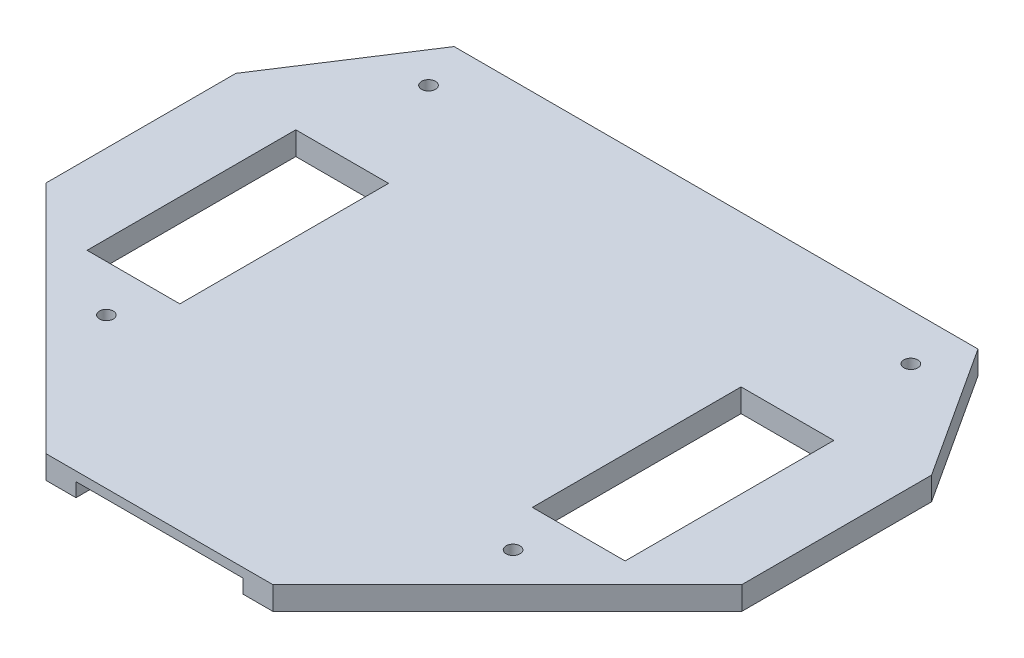
SolidWorks part; units mm, degrees
material "PMMA"
ref_plane "Front Plane" through (0, 0, 0) normal (0, 0, 1) x (1, 0, 0)
ref_plane "Top Plane" through (0, 0, 0) normal (0, 1, 0) x (1, 0, 0)
ref_plane "Right Plane" through (0, 0, 0) normal (1, 0, 0) x (0, 0, -1)
sketch "Sketch3" plane through (0, -40, 0) normal (0, -1, 0) x (-1, 0, 0)
  line L1 (27.5392, -110) -> (76.462, -110)
  line L2 (-23, -59.4608) -> (-23, -18.5314)
  line L3 (-4.4715, 10) -> (108.4727, 10)
  line L4 (127, -59.462) -> (127, -18.5295)
  line L5 (108.4727, 10) -> (127, -18.5295)
  line L6 (108.1379, 10.5156) -> (115.3271, -0.5548) construction
  line L7 (-4.4715, 10) -> (-23, -18.5314)
  line L8 (-17.9432, -10.7447) -> (2.4807, 20.7055) construction
  line L9 (127, -59.462) -> (76.462, -110)
  line L10 (52.0006, 10) -> (52.0006, -110) construction
  line L11 (27.5392, -110) -> (-23, -59.4608)
  dimension "D1" = 150
  dimension "D2" = 10
  dimension "D3" = 23
  dimension "D4" = 120
  dimension "D5" = 135
  dimension "D6" = 135
  dimension "D7" = 33
  dimension "D8" = 33
extrude "Boss-Extrude1" add sketch "Sketch3" along normal blind 5
hole_wizard "Ø3.0 (3) Diameter Hole1" positions "Sketch5" profile "Sketch4" hole size "Ø3.0" standard "ANSI Metric"
sketch "Sketch5" plane through (0, -45, 0) normal (0, -1, 0) x (-1, 0, 0)
  circle A0 centre (8.157, -77.6082) radius 1.5 construction
  circle A1 centre (95.8382, -77.6082) radius 1.5 construction
  circle A2 centre (103.9952, 0) radius 1.5 construction
  circle A3 centre (0, 0) radius 1.5 construction
  point P0 (8.157, -77.6082)
  point P3 (95.8382, -77.6082)
  point P6 (103.9952, 0)
  point P9 (0, 0)
sketch "Sketch4" plane through (-8.157, -45, 77.6082) normal (1, 0, 0) x (0, 0, -1)
  line L0 (0, 0) -> (0, 6.9013)
  line L1 (0, 6.9013) -> (1.5, 6)
  line L2 (1.5, 6) -> (1.5, 0)
  line L5 (1.5, 0) -> (0, 0)
  line L10 (0, 6.9013) -> (-1.5, 6) construction
  line L11 (0, -6.35) -> (0, 107.95) construction
  dimension "Hole Dia." = 3
  dimension "Hole Depth" = 6
  dimension "Drill Angle" = 118
sketch "Sketch6" plane through (0, -45, 0) normal (0, -1, 0) x (-1, 0, 0)
  line L0 (-23, -18.5314) -> (-23, -59.4608) construction
  line L1 (34, 7) -> (70, 7)
  line L2 (34, 7) -> (34, -117)
  line L3 (34, -117) -> (70, -117)
  line L4 (70, 7) -> (70, -117)
  line L6 (108.4727, 10) -> (-4.4715, 10) construction
  dimension "D1" = 124
  dimension "D2" = 36
  dimension "D3" = 57
  dimension "D4" = 3
extrude "Cut-Extrude1" cut sketch "Sketch6" against normal blind 3
sketch "Sketch9" plane through (0, -45, 0) normal (0, -1, 0) x (-1, 0, 0)
  line L1 (-6, -22.6082) -> (14, -22.6082)
  line L2 (-6, -22.6082) -> (-6, -67.6082)
  line L3 (-6, -67.6082) -> (14, -67.6082)
  line L4 (14, -22.6082) -> (14, -67.6082)
  line L5 (34, 7) -> (34, -110) construction
  dimension "D1" = 45
  dimension "D2" = 10
  dimension "D3" = 20
  dimension "D4" = 20
extrude "Cut-Extrude3" cut sketch "Sketch9" against normal through all
ref_plane "Plane2" through (-52, 0, 0) normal (-1, 0, 0) x (0, 0, 1)
mirror "Mirror1" about plane through (-52, 0, 0) normal (-1, 0, 0) of "Cut-Extrude3"
